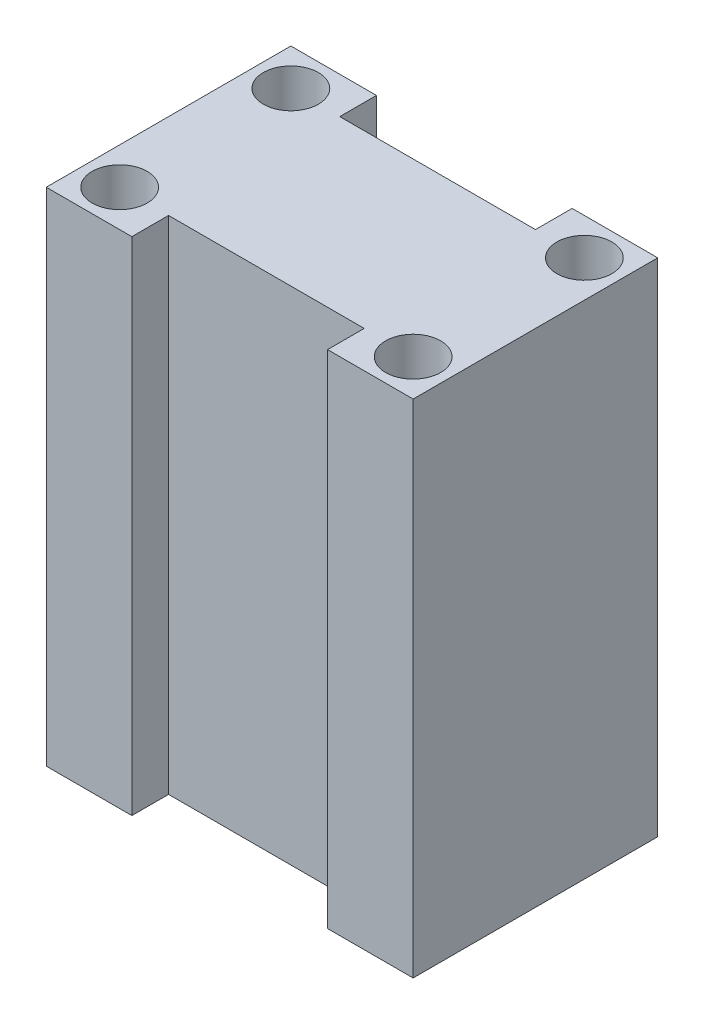
SolidWorks part; units mm, degrees
ref_plane "前视基准面" through (0, 0, 0) normal (0, 0, 1) x (1, 0, 0)
ref_plane "上视基准面" through (0, 0, 0) normal (0, 1, 0) x (1, 0, 0)
ref_plane "右视基准面" through (0, 0, 0) normal (1, 0, 0) x (0, 0, -1)
other "Configuration Table"
sketch "草图1" plane through (0, 0, 0) normal (0, 1, 0) x (1, 0, 0)
  line L1 (0, 0) -> (-30, 0)
  line L2 (0, 0) -> (0, 20)
  line L3 (0, 20) -> (-30, 20)
  line L4 (-30, 0) -> (-30, 20)
  dimension "D1" = 30
  dimension "D2" = 20
extrude "凸台-拉伸1" add sketch "草图1" along normal blind 41
sketch "草图17" plane through (0, 0, 0) normal (0, -1, 0) x (1, 0, 0)
  line L0 (-15, 0) -> (-15, -10) construction
  line L1 (-30, 0) -> (0, 0) construction
  line L2 (-23, -6) -> (-30, -6)
  line L7 (-23, -6) -> (-23, -14)
  line L8 (0, -14) -> (-7, -14)
  line L9 (-30, -20) -> (-30, 0) construction
  line L10 (-30, -14) -> (-23, -14)
  line L22 (-30, -6) -> (-30, -14)
  line L23 (0, -6) -> (0, -14)
  line L24 (-7, -6) -> (-7, -14)
  line L25 (-7, -6) -> (0, -6)
  line L26 (-15, -10) -> (-16.9272, -10) construction
  line L27 (-23, 0) -> (-7, 0)
  line L28 (-23, 0) -> (-23, -3)
  line L29 (-23, -3) -> (-7, -3)
  line L30 (-7, 0) -> (-7, -3)
  line L31 (-23, -17) -> (-7, -17)
  line L32 (-7, -20) -> (-7, -17)
  line L33 (-23, -20) -> (-7, -20)
  line L34 (-23, -20) -> (-23, -17)
  dimension "D1" = 3
  dimension "D2" = 16
  dimension "D3" = 7
extrude "切除-拉伸15" cut sketch "草图17" against normal up to next
sketch "草图20" plane through (0, 41, 0) normal (0, 1, 0) x (1, 0, 0)
  line L0 (-30, 0) -> (-27, 0) construction
  line L1 (-30, 0) -> (-23, 0) construction
  line L2 (-27, 0) -> (-27, 3) construction
  line L3 (-27, 3) -> (-27, 17) construction
  line L4 (-27, 17) -> (-3, 17) construction
  line L5 (-3, 17) -> (-3, 3) construction
  circle A0 centre (-27, 17) radius 2.25
  circle A1 centre (-27, 3) radius 2.25
  circle A2 centre (-3, 3) radius 2.25
  circle A3 centre (-3, 17) radius 2.25
  dimension "D6" = 4.5
  dimension "D1" = 3
  dimension "D2" = 3
  dimension "D3" = 14
  dimension "D4" = 24
  dimension "D5" = 14
extrude "切除-拉伸18" cut sketch "草图20" against normal blind 5
sketch "草图21" plane through (-7, 0, 0) normal (1, 0, 0) x (0, 0, -1)
  line L4 (6, 41) -> (6, 0)
  line L5 (6, 0) -> (14, 0)
  line L6 (14, 0) -> (14, 41)
  line L7 (14, 41) -> (6, 41)
  line L8 (6, 41) -> (6, 0)
  line L9 (6, 0) -> (14, 0)
  line L10 (14, 0) -> (14, 41)
  line L11 (14, 41) -> (6, 41)
  dimension "D1" = 0
extrude "凸台-拉伸2" add sketch "草图21" along normal up to surface (7 mm away) up to face at (0, 20.5, -17)
sketch "草图22" plane through (-23, 0, 0) normal (-1, 0, 0) x (0, 0, 1)
  line L4 (-14, 41) -> (-14, 0)
  line L5 (-14, 0) -> (-6, 0)
  line L6 (-6, 0) -> (-6, 41)
  line L7 (-6, 41) -> (-14, 41)
  line L8 (-14, 41) -> (-14, 0)
  line L9 (-14, 0) -> (-6, 0)
  line L10 (-6, 0) -> (-6, 41)
  line L11 (-6, 41) -> (-14, 41)
  dimension "D1" = 0
extrude "凸台-拉伸3" add sketch "草图22" along normal up to surface (7 mm away) up to face at (-30, 20.5, -17)
sketch "草图23" plane through (0, 0, 0) normal (0, -1, 0) x (1, 0, 0)
  circle A0 centre (-3, -17) radius 2.25 construction
  circle A1 centre (-27, -17) radius 2.25 construction
  circle A2 centre (-27, -3) radius 2.25 construction
  circle A3 centre (-3, -3) radius 2.25 construction
  circle A4 centre (-3, -17) radius 2.25
  circle A5 centre (-27, -17) radius 2.25
  circle A6 centre (-27, -3) radius 2.25
  circle A7 centre (-3, -3) radius 2.25
extrude "切除-拉伸19" cut sketch "草图23" against normal blind 5
sketch "草图24" plane through (0, 5, 0) normal (0, -1, 0) x (1, 0, 0)
  circle A0 centre (-27, -3) radius 1.5
  circle A1 centre (-3, -3) radius 1.5
  circle A2 centre (-27, -17) radius 1.5
  circle A3 centre (-3, -17) radius 1.5
  dimension "D1" = 3
  dimension "D2" = 3
  dimension "D3" = 3
  dimension "D4" = 3
extrude "切除-拉伸20" cut sketch "草图24" against normal blind 4
sketch "草图25" plane through (0, 36, 0) normal (0, 1, 0) x (1, 0, 0)
  circle A0 centre (-27, 17) radius 1.5 construction
  circle A1 centre (-3, 17) radius 1.5 construction
  circle A2 centre (-3, 3) radius 1.5 construction
  circle A3 centre (-27, 3) radius 1.5 construction
  circle A4 centre (-27, 17) radius 1.5
  circle A5 centre (-3, 17) radius 1.5
  circle A6 centre (-3, 3) radius 1.5
  circle A7 centre (-27, 3) radius 1.5
extrude "切除-拉伸21" cut sketch "草图25" against normal blind 4
